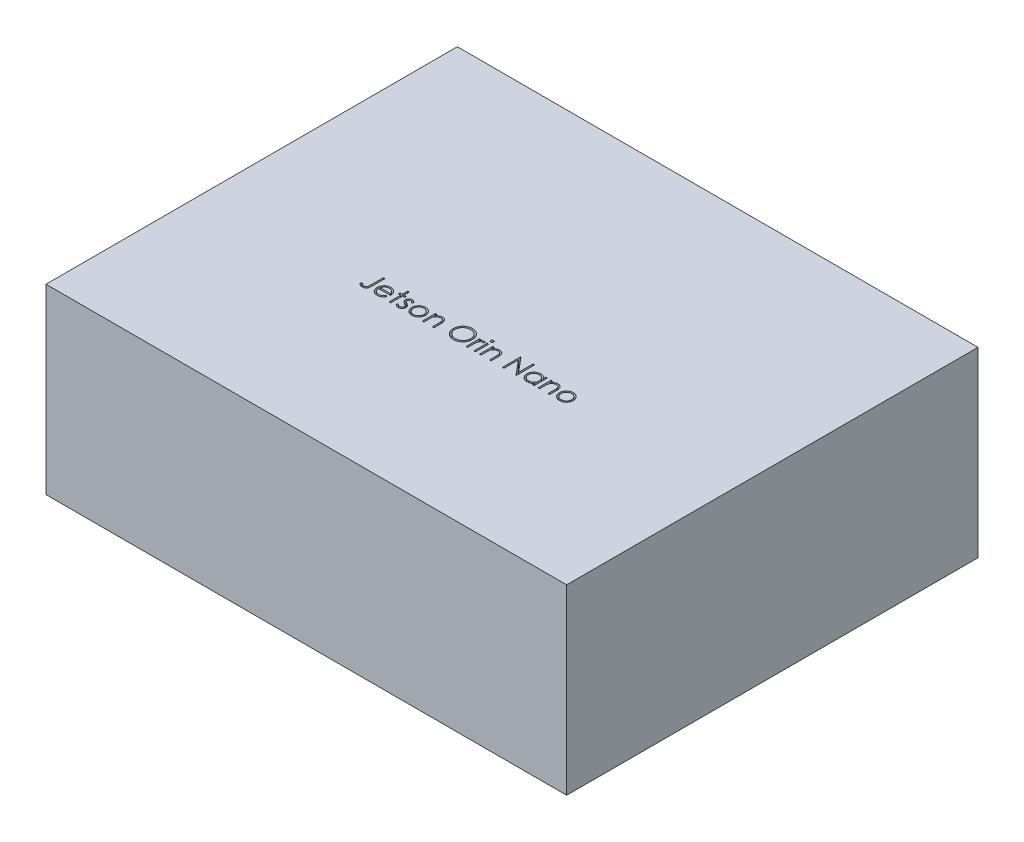
SolidWorks part; units mm, degrees
ref_plane "Front Plane" through (0, 0, 0) normal (0, 0, 1) x (1, 0, 0)
ref_plane "Top Plane" through (0, 0, 0) normal (0, 1, 0) x (1, 0, 0)
ref_plane "Right Plane" through (0, 0, 0) normal (1, 0, 0) x (0, 0, -1)
sketch "Sketch1" plane through (0, 0, 0) normal (0, 1, 0) x (1, 0, 0)
  line L1 (0, 0) -> (100, 0)
  line L2 (0, 0) -> (0, 79)
  line L3 (0, 79) -> (100, 79)
  line L4 (100, 0) -> (100, 79)
  dimension "D1" = 100
  dimension "D2" = 79
extrude "Boss-Extrude1" add sketch "Sketch1" along normal blind 35
sketch "Sketch2" plane through (0, 35, 0) normal (0, 1, 0) x (1, 0, 0)
  line L0 (0, 30) -> (100, 30) construction
  line L1 (0, 79) -> (0, 0) construction
  line L2 (100, 0) -> (100, 79) construction
  line L3 (0, 0) -> (100, 0) construction
  text T0 "Jetson Orin Nano"
  dimension "D1" = 30
extrude "Cut-Extrude1" cut sketch "Sketch2" against normal blind 5
